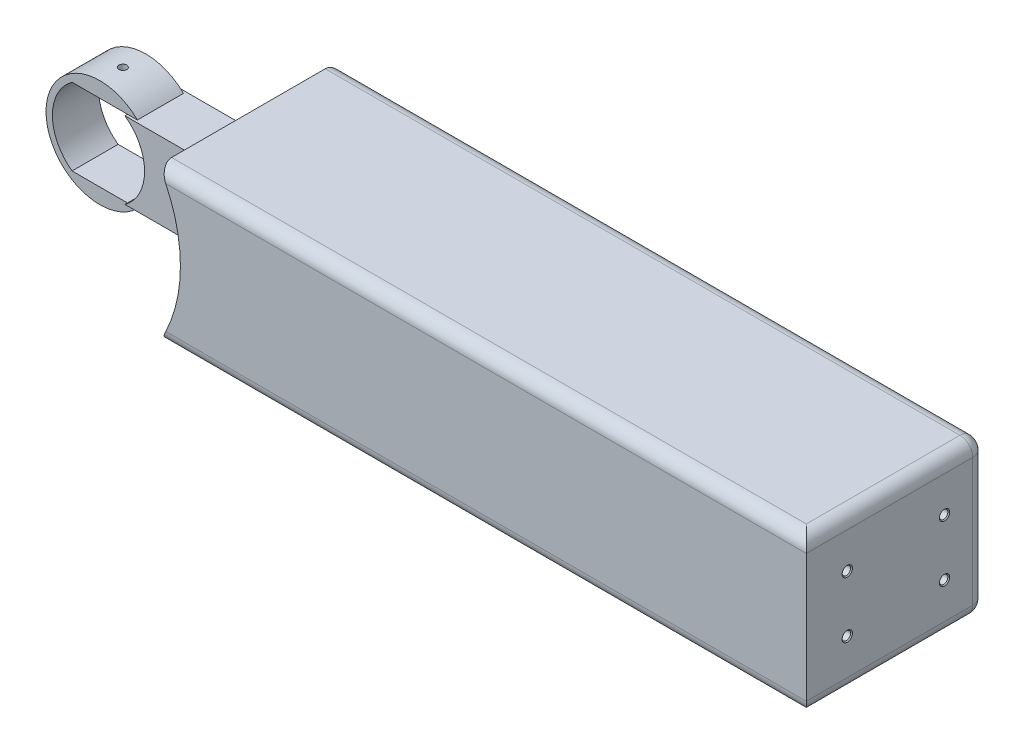
SolidWorks part; units mm, degrees
note: The reader was unsure of these and kept them because the rebuilt part matched: shared geometry of "Sketch10<3>".
ref_plane "Front Plane" through (0, 0, 0) normal (0, 0, 1) x (1, 0, 0)
ref_plane "Top Plane" through (0, 0, 0) normal (0, 1, 0) x (1, 0, 0)
ref_plane "Right Plane" through (0, 0, 0) normal (1, 0, 0) x (0, 0, -1)
sketch "Sketch2" plane through (0, 0, 0) normal (1, 0, 0) x (0, 0, -1)
  line L0 (-7, 12) -> (7, 12)
  line L5 (-9, 14) -> (9, -14) construction
  line L6 (-9, -14) -> (9, 14) construction
  line L7 (-10, 15) -> (10, 15)
  line L8 (-10, 15) -> (-10, -15)
  line L9 (-10, -15) -> (10, -15)
  line L10 (10, 15) -> (10, -15)
  line L11 (-10, 15) -> (10, -15) construction
  line L12 (-10, -15) -> (10, 15) construction
  line L13 (7, 12) -> (7, -12)
  line L14 (-7, -12) -> (7, -12)
  line L15 (-7, 12) -> (-7, -12)
  point P0 (0, 0)
  point P1 (0, 0)
  point P7 (0, 0)
  dimension "D5" = 3
  dimension "D1" = 30
  dimension "D2" = 20
  dimension "D3" = 18
  dimension "D4" = 28
extrude "Boss-Extrude1" add sketch "Sketch2" along normal blind 302
ref_plane "Sketch8" through (302, 0, 0) normal (1, 0, 0) x (0, 0, -1)
sketch "Sketch9" plane through (302, 0, 0) normal (1, 0, 0) x (0, 0, -1)
  line L0 (23, -10.5143) -> (23, -42.094) construction
  line L1 (-35, -30) -> (35, -30)
  line L2 (0, -26.0523) -> (0, 26.0523)
  line L3 (-35, 30) -> (35, 30)
  line L4 (35, -30) -> (35, 30)
  line L5 (0, 0) -> (41.0566, 0) construction
  line L6 (23, 45.0661) -> (23, -5.5143) construction
  line L7 (-35, -30) -> (-35, 30)
  line L8 (10, 0) -> (0, 0) construction
  line L9 (10, -15) -> (10, 15) construction
  point P9 (23, 0)
  point P12 (23, 0)
  point P13 (23, 13)
  point P14 (23, -13)
  dimension "D1" = 30
  dimension "D2" = 30
  dimension "D3" = 35
  dimension "D4" = 23
  dimension "D5" = 13
  dimension "D6" = 13
extrude "Boss-Extrude2" add sketch "Sketch9" against normal blind 3
sketch "Sketch10" plane through (0, 0, 0) normal (0, 0, 1) x (1, 0, 0)
  line L1 (0, 15) -> (0, -15) construction
  line L2 (0, 0) -> (0, 19.4509) construction
  line L3 (0, 19.4509) -> (0, -17.2685) construction
  line L4 (10.8282, -15) -> (-10.8282, -15)
  line L5 (10.8282, 15) -> (-10.8282, 15)
  circle A0 centre (0, 0) radius 21
  circle A1 centre (0, 0) radius 18.5
  point P0 (0, 0)
  point P6 (0, 15)
  point P10 (0, -15)
  dimension "D1" = 42
  dimension "D2" = 37
  dimension "D3" = 15
  dimension "D4" = 15
extrude "Boss-Extrude3" add sketch "Sketch10" along normal blind 9 and the other way blind 9 contours L5 A1 | A0 A1 | L4 A1
extrude "Cut-Extrude1" cut sketch "Sketch10<3>" against normal blind 19 and the other way blind 19 contours L5 A1 L4
sketch "Sketch10<3>" plane through (0, 0, 0) normal (0, 0, 1) x (1, 0, 0) same geometry as "Sketch10"
sketch "Sketch14" plane through (299, 0, 0) normal (-1, 0, 0) x (0, 0, 1)
  line L4 (35, -30) -> (35, 30)
  line L5 (35, 30) -> (-35, 30)
  line L6 (-35, 30) -> (-35, -30)
  line L7 (-35, -30) -> (35, -30)
  line L8 (35, -30) -> (35, 30)
  line L9 (35, 30) -> (-35, 30)
  line L10 (-35, 30) -> (-35, -30)
  line L11 (-35, -30) -> (35, -30)
  dimension "D1" = 0
extrude "Boss-Extrude5" add sketch "Sketch14" along normal blind 10
sketch "Sketch15" plane through (289, 0, 0) normal (-1, 0, 0) x (0, 0, 1)
  line L0 (30, 25) -> (-30, 25)
  line L1 (-30, 25) -> (-30, -25)
  line L2 (-30, -25) -> (30, -25)
  line L3 (30, -25) -> (30, 25)
  line L4 (-35, -30) -> (35, -30)
  line L5 (35, -30) -> (35, 30)
  line L6 (35, 30) -> (-35, 30)
  line L7 (-35, 30) -> (-35, -30)
  line L8 (-35, -30) -> (35, -30)
  line L9 (35, -30) -> (35, 30)
  line L10 (35, 30) -> (-35, 30)
  line L11 (-35, 30) -> (-35, -30)
  dimension "D1" = 0
  dimension "D2" = 5
extrude "Boss-Extrude6" add sketch "Sketch15" along normal up to surface (239.9465 mm away)
sketch "Sketch16" plane through (0, 15, 0) normal (0, 1, 0) x (1, 0, 0)
  line L8 (54.6125, 10) -> (302, 10)
  line L9 (54.6125, 10) -> (54.6125, -10)
  line L10 (54.6125, -10) -> (302, -10)
  line L11 (302, 10) -> (302, -10)
  line L13 (302, -33) -> (302, 33) construction
  line L14 (289, 10) -> (10.8282, 10) construction
  line L15 (289, -10) -> (10.8282, -10) construction
extrude "Boss-Extrude7" add sketch "Sketch16" along normal up to surface (10 mm away) up to face at (170.3904, 25, 0)
fillet "Fillet1" radius 5 7 edges at (302, 30, 0) (302, -30, 0) (302, 0, -35) (175.5268, 30, -35) (175.5268, -30, -35) (175.5268, -30, 35) (175.5268, 30, 35)
hole_wizard "M4 Tapped Hole1" positions "Sketch17" profile "Sketch18" tap size "M4" standard "ISO"
sketch "Sketch17" plane through (302, 0, 0) normal (1, 0, 0) x (0, 0, -1)
  point P0 (-19, 11)
  point P3 (19, 11)
  point P6 (-19, -11)
  point P9 (19, -11)
sketch "Sketch18" plane through (302, 11, 19) normal (0, 1, 0) x (0, 0, -1)
  line L0 (0, 0) -> (0, 9)
  line L1 (0, 9) -> (1.65, 8.0086)
  line L2 (1.65, 8.0086) -> (1.65, 0.375)
  line L3 (1.65, 0.375) -> (2.025, 0)
  line L5 (2.025, 0) -> (0, 0)
  line L6 (-1.65, 0.375) -> (-2.025, 0) construction
  line L10 (0, 9) -> (-1.65, 8.0086) construction
  line L11 (0, -6.35) -> (0, 107.95) construction
  dimension "Tap Drill Dia." = 3.3
  dimension "Tap Drill Depth" = 9
  dimension "Near C'Sink Dia." = 4.05
  dimension "Near C'Sink Angle" = 90
  dimension "Drill Angle" = 118
cosmetic thread "Hole Thread1" parameters "D1"=8, "D2"=4
cosmetic thread "Hole Thread2" parameters "D1"=8, "D2"=4
cosmetic thread "Hole Thread3" parameters "D1"=8, "D2"=4
cosmetic thread "Hole Thread4" parameters "D1"=8, "D2"=4
sketch "Sketch19" plane through (0, 15, 0) normal (0, -1, 0) x (1, 0, 0)
  circle A0 centre (0, 0) radius 1.525
  dimension "D1" = 3.05
extrude "Cut-Extrude3" cut sketch "Sketch19" against normal blind 10
